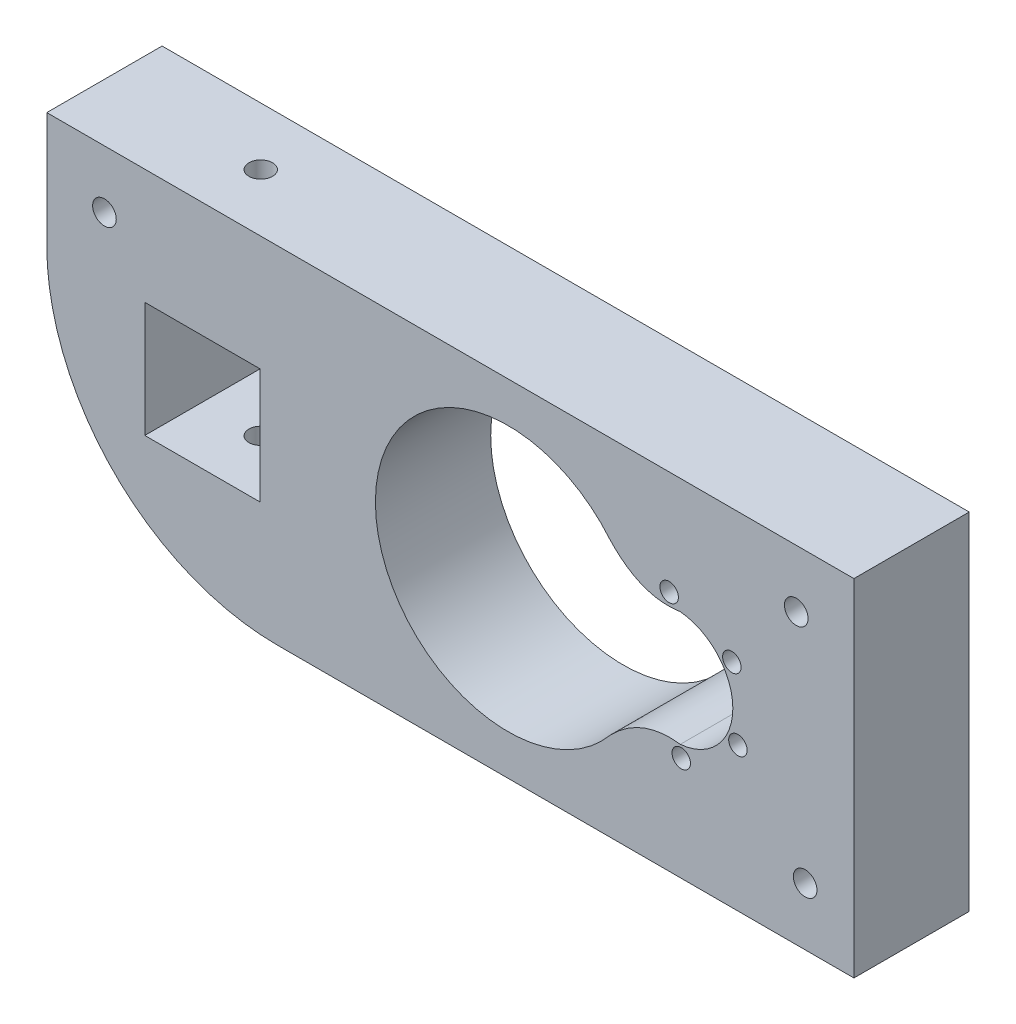
SolidWorks part; units mm, degrees
ref_plane "Plan de face" through (0, 0, 0) normal (0, 0, 1) x (1, 0, 0)
ref_plane "Plan de dessus" through (0, 0, 0) normal (0, 1, 0) x (1, 0, 0)
ref_plane "Plan de droite" through (0, 0, 0) normal (1, 0, 0) x (0, 0, -1)
sketch "Esquisse1" plane through (0, 0, 0) normal (0, 0, 1) x (1, 0, 0)
  line L1 (0, 0) -> (70, 0)
  line L2 (0, 0) -> (0, 30)
  line L3 (0, 30) -> (70, 30)
  line L4 (70, 0) -> (70, 30)
  dimension "D1" = 30
  dimension "D2" = 70
extrude "Boss.-Extru.1" add sketch "Esquisse1" along normal blind 10
sketch "Esquisse2" plane through (0, 0, 10) normal (0, 0, 1) x (1, 0, 0)
  line L0 (66.0915, 15) -> (-1.5751, 15) construction
  line L1 (54.5, 34.4565) -> (54.5, -6.8023) construction
  line L2 (70, 30) -> (0, 30) construction
  line L4 (0, 30) -> (0, 0) construction
  arc A0 (54.9408, 19.9805) -> (54.9408, 10.0195) centre (54.5, 15) cw
  circle A2 centre (53.9746, 20.9769) radius 0.8
  circle A3 centre (59.4135, 18.4435) radius 0.8
  circle A4 centre (59.9389, 12.4666) radius 0.8
  circle A5 centre (55.0254, 9.0231) radius 0.8
  arc A6 (48.86, 22.3315) -> (48.86, 7.6685) centre (40, 15) ccw
  circle A8 centre (49.0611, 17.5334) radius 0.8 [skipped]
  circle A9 centre (49.5865, 11.5565) radius 0.8 [skipped]
  spline S0 degree 2 poles (48.86, 22.3315) (51.5345, 19.4593) (54.9408, 19.9805) knots 0 0 0 1 1 1
  spline S1 degree 2 poles (48.86, 7.6685) (51.5403, 10.446) (54.9408, 10.0195) knots 0 0 0 1 1 1
  point P18 (54.5, 15)
  point P32 (59.5, 15)
  dimension "D1" = 11.5
  dimension "D2" = 5
  dimension "D3" = 1.6
  dimension "D5" = 14.5
  dimension "D8" = 10.64
  dimension "D6" = 15
  dimension "D7" = 40
  dimension "D9" = 10.64
  dimension "D10" = 8.86
  dimension "D11" = 4.7
  dimension "D12" = 4.7
  dimension "D13" = 5.9769
  dimension "D14" = 6
  dimension "D4" = 6
extrude "Enlèv. mat.-Extru.1" cut sketch "Esquisse2" against normal through all
sketch "Esquisse3" plane through (0, 0, 10) normal (0, 0, 1) x (1, 0, 0)
  line L1 (70, 0) -> (70, 30) construction
  line L2 (70, 30) -> (0, 30) construction
  circle A0 centre (5, 25) radius 1.025
  circle A2 centre (65.7711, 5) radius 1.025
  circle A3 centre (65, 25) radius 1.025
  dimension "D2" = 2.05
  dimension "D6" = 2.05
  dimension "D7" = 2.05
  dimension "D9" = 5
  dimension "D10" = 5
  dimension "D8" = 4.2289
extrude "Enlèv. mat.-Extru.2" cut sketch "Esquisse3" against normal through all
fillet "Congé2" radius 20 1 edges at (0, 0, 5)
sketch "Esquisse4" plane through (0, 0, 10) normal (0, 0, 1) x (1, 0, 0)
  line L4 (0, 30) -> (0, 20)
  line L5 (20, 0) -> (70, 0)
  line L6 (70, 0) -> (70, 30)
  line L7 (70, 30) -> (0, 30)
  line L8 (0, 30) -> (0, 20)
  line L9 (20, 0) -> (70, 0)
  line L10 (70, 0) -> (70, 30)
  line L11 (70, 30) -> (0, 30)
  line L12 (18.5, 20) -> (18.5, 10)
  line L13 (8.5, 20) -> (18.5, 20)
  line L14 (18.5, 10) -> (8.5, 10)
  line L15 (8.5, 10) -> (8.5, 20)
  arc A1 (0, 20) -> (20, 0) centre (20, 20) ccw
  arc A2 (0, 20) -> (20, 0) centre (20, 20) ccw
  dimension "D1" = 0
extrude "Enlèv. mat.-Extru.3" cut sketch "Esquisse4" against normal through all flip side to cut
sketch "Esquisse6" plane through (0, 30, 0) normal (0, 1, 0) x (1, 0, 0)
  line L0 (13.5567, -10) -> (13.5567, 0) construction
  line L1 (70, -10) -> (0, -10) construction
  line L2 (70, 0) -> (0, 0) construction
  circle A0 centre (13.5567, -5) radius 1.025
  dimension "D1" = 2.05
  dimension "D2" = 5
extrude "Enlèv. mat.-Extru.4" cut sketch "Esquisse6" against normal through all
